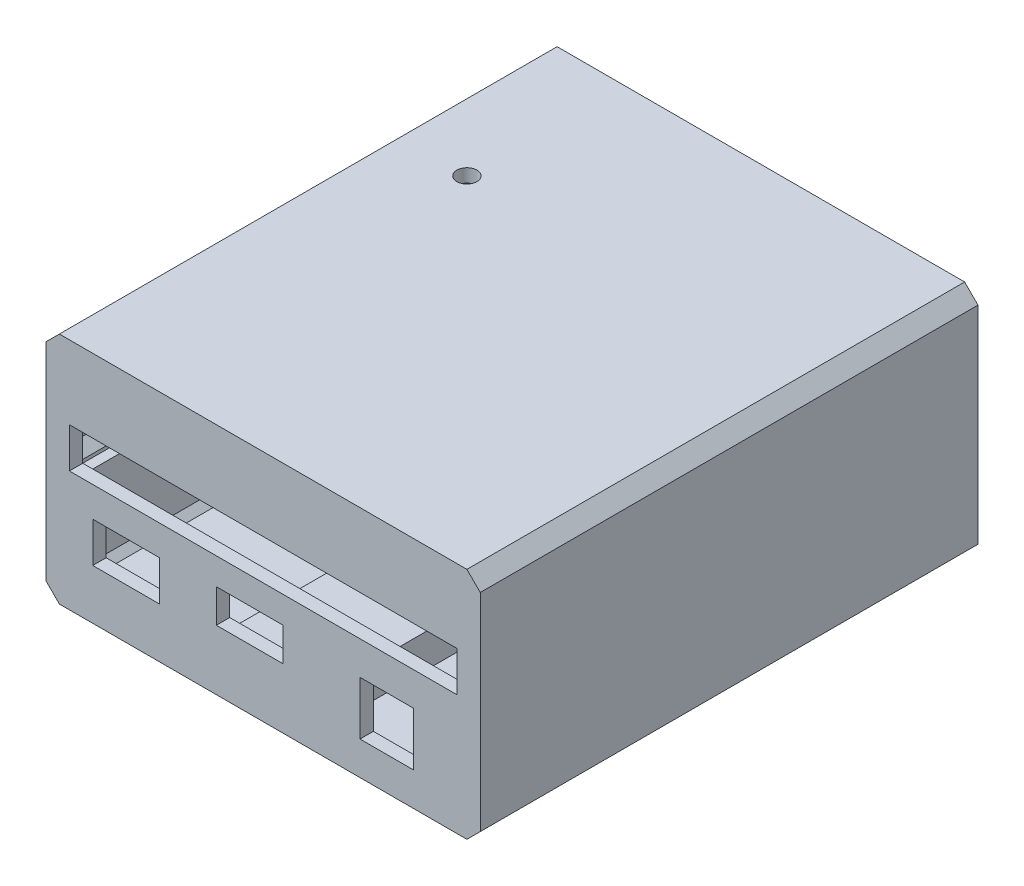
SolidWorks part; units mm, degrees
ref_plane "Alzado" through (0, 0, 0) normal (0, 0, 1) x (1, 0, 0)
ref_plane "Planta" through (0, 0, 0) normal (0, 1, 0) x (1, 0, 0)
ref_plane "Vista lateral" through (0, 0, 0) normal (1, 0, 0) x (0, 0, -1)
sketch "Croquis1" plane through (0, 0, 0) normal (0, 0, 1) x (1, 0, 0)
  line L0 (-29, 6.5) -> (-29, 0.5)
  line L1 (-32.5, -17.5) -> (32.5, -17.5)
  line L2 (-32.5, -17.5) -> (-32.5, 17.5)
  line L3 (-32.5, 17.5) -> (32.5, 17.5)
  line L4 (32.5, -17.5) -> (32.5, 17.5)
  line L5 (-32.5, -17.5) -> (32.5, 17.5) construction
  line L6 (-32.5, 17.5) -> (32.5, -17.5) construction
  line L7 (-32.5, 0.5) -> (32.5, 0.5)
  line L8 (-32.5, 0.5) -> (-32.5, 6.5)
  line L9 (-32.5, 6.5) -> (32.5, 6.5)
  line L10 (32.5, 0.5) -> (32.5, 6.5)
  line L11 (29, 6.5) -> (29, 0.5)
  line L13 (-7, -8.5) -> (3, -8.5)
  line L14 (-7, -8.5) -> (-7, -3.5)
  line L15 (-7, -3.5) -> (3, -3.5)
  line L16 (3, -8.5) -> (3, -3.5)
  line L17 (-7, -8.5) -> (3, -3.5) construction
  line L18 (-7, -3.5) -> (3, -8.5) construction
  line L19 (14.5, -12.5) -> (22.5, -12.5)
  line L20 (14.5, -12.5) -> (14.5, -4.5)
  line L21 (14.5, -4.5) -> (22.5, -4.5)
  line L22 (22.5, -12.5) -> (22.5, -4.5)
  line L23 (14.5, -12.5) -> (22.5, -4.5) construction
  line L24 (14.5, -4.5) -> (22.5, -12.5) construction
  line L25 (-25.5, -4) -> (-15.5, -4)
  line L26 (-25.5, -4) -> (-25.5, -10)
  line L27 (-25.5, -10) -> (-15.5, -10)
  line L28 (-15.5, -4) -> (-15.5, -10)
  line L29 (-25.5, -4) -> (-15.5, -10) construction
  line L30 (-25.5, -10) -> (-15.5, -4) construction
  point P0 (0, 0)
  point P14 (18.5, -8.5)
  point P15 (-2, -6)
  point P24 (-20.5, -7)
  dimension "D1" = 35
  dimension "D2" = 65
  dimension "D3" = 0.5
  dimension "D4" = 6
  dimension "D5" = 3.5
  dimension "D6" = 3.5
  dimension "D7" = 10
  dimension "D8" = 5
  dimension "D9" = 6
  dimension "D10" = 8
  dimension "D11" = 8
  dimension "D12" = 12
  dimension "D13" = 30.5
  dimension "D14" = 6
  dimension "D15" = 10
  dimension "D16" = 7
  dimension "D17" = 9
  dimension "D18" = 51
extrude "Saliente-Extruir1" add sketch "Croquis1" along normal blind 2 contours L2 L9 L4 L3 | L9 L2 L7 L0 | L9 L11 L7 L4 | L7 L2 L1 L4 L22 L19 L20 L21 L16 L13 L14 L15 L25 L28 L27 L26
sketch "Croquis2" plane through (0, 0, 0) normal (0, 0, -1) x (-1, 0, 0)
  line L0 (30.5, 15.5) -> (-30.5, 15.5)
  line L1 (-30.5, 15.5) -> (-30.5, -15.5)
  line L2 (-30.5, -15.5) -> (30.5, -15.5)
  line L3 (30.5, -15.5) -> (30.5, 15.5)
  line L4 (-32.5, -17.5) -> (32.5, -17.5)
  line L5 (32.5, -17.5) -> (32.5, 17.5)
  line L6 (32.5, 17.5) -> (-32.5, 17.5)
  line L7 (-32.5, 17.5) -> (-32.5, -17.5)
  line L8 (-32.5, -17.5) -> (32.5, -17.5)
  line L9 (32.5, -17.5) -> (32.5, 17.5)
  line L10 (32.5, 17.5) -> (-32.5, 17.5)
  line L11 (-32.5, 17.5) -> (-32.5, -17.5)
  dimension "D1" = 0
  dimension "D2" = 2
extrude "Saliente-Extruir2" add sketch "Croquis2" along normal blind 71
sketch "Croquis3" plane through (0, 0, 0) normal (0, 0, -1) x (-1, 0, 0)
  line L0 (-30.5, 0) -> (30.5, 0) construction
  line L1 (-30.5, 15.5) -> (-30.5, -15.5) construction
  line L2 (30.5, -15.5) -> (30.5, 15.5) construction
  line L3 (-30.5, 1) -> (-29, 1)
  line L4 (-29, 1) -> (-30.5, 2.5)
  line L5 (-30.5, 1) -> (-30.5, 2.5)
  line L6 (-30.5, -1) -> (-30.5, -2.5)
  line L7 (-29, -1) -> (-30.5, -2.5)
  line L8 (-30.5, -1) -> (-29, -1)
  line L9 (0, 15.5) -> (0, -15.5) construction
  line L10 (30.5, 15.5) -> (-30.5, 15.5) construction
  line L11 (-30.5, -15.5) -> (30.5, -15.5) construction
  line L12 (30.5, -1) -> (29, -1)
  line L13 (29, -1) -> (30.5, -2.5)
  line L14 (30.5, -1) -> (30.5, -2.5)
  line L15 (30.5, 1) -> (30.5, 2.5)
  line L16 (29, 1) -> (30.5, 2.5)
  line L17 (30.5, 1) -> (29, 1)
  dimension "D1" = 1.5
  dimension "D2" = 1.5
  dimension "D3" = 1
extrude "Saliente-Extruir3" add sketch "Croquis3" along normal blind 70
sketch "Croquis9" plane through (0, 17.5, 0) normal (0, 1, 0) x (1, 0, 0)
  circle A0 centre (-20.5, 49) radius 1.5
  dimension "D1" = 20.5
  dimension "D3" = 3
  dimension "D4" = 49
extrude "Cortar-Extruir2" cut sketch "Croquis9" against normal up to next
chamfer "Chaflán3" distance 2 angle 45 4 edges at (32.5, -17.5, -34.5) (-32.5, -17.5, -34.5) (32.5, 17.5, -34.5) (-32.5, 17.5, -34.5)
chamfer "Chaflán2" distance 1 angle 45 4 edges at (-30.5, 15.5, -35.5) (-30.5, -15.5, -35.5) (30.5, -15.5, -35.5) (30.5, 15.5, -35.5)
sketch "Sketch1" plane through (0, 0, -71) normal (0, 0, -1) x (-1, 0, 0)
  line L0 (-31.55, 15.1065) -> (-31.55, -15.1065)
  line L1 (-31.55, -15.1065) -> (-30.1065, -16.55)
  line L2 (-30.1065, -16.55) -> (30.1065, -16.55)
  line L3 (30.1065, -16.55) -> (31.55, -15.1065)
  line L4 (31.55, -15.1065) -> (31.55, 15.1065)
  line L5 (31.55, 15.1065) -> (30.1065, 16.55)
  line L6 (30.1065, 16.55) -> (-30.1065, 16.55)
  line L7 (-30.1065, 16.55) -> (-31.55, 15.1065)
  line L8 (-32.5, 15.5) -> (-32.5, -15.5)
  line L9 (-32.5, -15.5) -> (-30.5, -17.5)
  line L10 (-30.5, -17.5) -> (30.5, -17.5)
  line L11 (30.5, -17.5) -> (32.5, -15.5)
  line L12 (32.5, -15.5) -> (32.5, 15.5)
  line L13 (32.5, 15.5) -> (30.5, 17.5)
  line L14 (30.5, 17.5) -> (-30.5, 17.5)
  line L15 (-30.5, 17.5) -> (-32.5, 15.5)
  line L16 (-32.5, 15.5) -> (-32.5, -15.5)
  line L17 (-32.5, -15.5) -> (-30.5, -17.5)
  line L18 (-30.5, -17.5) -> (30.5, -17.5)
  line L19 (30.5, -17.5) -> (32.5, -15.5)
  line L20 (32.5, -15.5) -> (32.5, 15.5)
  line L21 (32.5, 15.5) -> (30.5, 17.5)
  line L22 (30.5, 17.5) -> (-30.5, 17.5)
  line L23 (-30.5, 17.5) -> (-32.5, 15.5)
  dimension "D1" = 0
  dimension "D2" = 0.95
extrude "Boss-Extrude1" add sketch "Sketch1" along normal blind 1.5
chamfer "Chamfer1" distance 0.1 distance2 1.5 8 edges at (0, -16.55, -72.5) (-30.8282, -15.8282, -72.5) (-31.55, 0, -72.5) (-30.8282, 15.8282, -72.5) (0, 16.55, -72.5) (30.8282, 15.8282, -72.5) (31.55, 0, -72.5) (30.8282, -15.8282, -72.5)
sketch "Sketch2" plane through (0, 0, -72.5) normal (0, 0, -1) x (-1, 0, 0)
  line L0 (-31.65, -15.1479) -> (-31.65, 15.1479) construction
  line L1 (-32.15, -1) -> (-31.15, -1)
  line L2 (-32.15, -1) -> (-32.15, 1)
  line L3 (-32.15, 1) -> (-31.15, 1)
  line L4 (-31.15, -1) -> (-31.15, 1)
  line L5 (-32.15, -1) -> (-31.15, 1) construction
  line L6 (-32.15, 1) -> (-31.15, -1) construction
  line L7 (31.65, 15.1479) -> (31.65, -15.1479) construction
  line L8 (31.15, -1) -> (32.15, -1)
  line L9 (31.15, -1) -> (31.15, 1)
  line L10 (31.15, 1) -> (32.15, 1)
  line L11 (32.15, -1) -> (32.15, 1)
  line L12 (31.15, -1) -> (32.15, 1) construction
  line L13 (31.15, 1) -> (32.15, -1) construction
  point P0 (-31.65, 0)
  point P7 (31.65, 0)
  dimension "D1" = 2
  dimension "D2" = 1
  dimension "D3" = 1
  dimension "D4" = 2
extrude "Boss-Extrude2" add sketch "Sketch2" against normal blind 0.5
sketch "Sketch3" plane through (0, -17.5, 0) normal (0, -1, 0) x (1, 0, 0)
  line L0 (0, 2) -> (0, -18) construction
  line L1 (-30.5, 2) -> (30.5, 2) construction
  line L3 (7.5, -8) -> (-7.5, -8)
  line L4 (7.5, -8) -> (7.5, -28)
  line L5 (7.5, -28) -> (-7.5, -28)
  line L6 (-7.5, -8) -> (-7.5, -28)
  line L7 (7.5, -8) -> (-7.5, -28) construction
  line L8 (7.5, -28) -> (-7.5, -8) construction
  dimension "D1" = 20
  dimension "D2" = 15
  dimension "D3" = 20
extrude "Boss-Extrude3" add sketch "Sketch3" against normal blind 7
sketch "Sketch4" plane through (0, -17.5, 0) normal (0, -1, 0) x (1, 0, 0)
  line L0 (0, 2) -> (0, -18) construction
  line L1 (-30.5, 2) -> (30.5, 2) construction
  line L3 (-6.5, -27) -> (6.5, -27)
  line L4 (-6.5, -27) -> (-6.5, -9)
  line L5 (-6.5, -9) -> (6.5, -9)
  line L6 (6.5, -27) -> (6.5, -9)
  line L7 (-6.5, -27) -> (6.5, -9) construction
  line L8 (-6.5, -9) -> (6.5, -27) construction
  dimension "D1" = 20
  dimension "D2" = 13
  dimension "D3" = 18
extrude "Cut-Extrude1" cut sketch "Sketch4" against normal blind 5
sketch "Sketch5" plane through (0, 0, -9) normal (0, 0, -1) x (-1, 0, 0)
  line L1 (6.5, -17.5) -> (-6.5, -17.5)
  line L2 (6.5, -17.5) -> (6.5, -15)
  line L3 (6.5, -15) -> (-6.5, -15)
  line L4 (-6.5, -17.5) -> (-6.5, -15)
  line L5 (-6.5, -12.5) -> (-6.5, -17.5) construction
  point P4 (-6.0318, -15.0053)
  point P7 (0, 0)
  dimension "D1" = 2.5
extrude "Boss-Extrude4" add sketch "Sketch5" along normal blind 12
chamfer "Chamfer2" distance 5 angle 60 1 edges at (0, -15.5, -28)
chamfer "Chamfer3" distance 5 angle 60 1 edges at (0, -17.5, -27)
chamfer "Chamfer4" distance 3 angle 30 1 edges at (0, -15, -21)
sketch "Sketch6" plane through (0, 0, -8) normal (0, 0, 1) x (1, 0, 0)
  line L4 (-7.5, -10.5) -> (-7.5, -15.5)
  line L5 (-7.5, -15.5) -> (7.5, -15.5)
  line L6 (7.5, -15.5) -> (7.5, -10.5)
  line L7 (7.5, -10.5) -> (-7.5, -10.5)
  line L8 (-7.5, -10.5) -> (-7.5, -15.5)
  line L9 (-7.5, -15.5) -> (7.5, -15.5)
  line L10 (7.5, -15.5) -> (7.5, -10.5)
  line L11 (7.5, -10.5) -> (-7.5, -10.5)
  dimension "D1" = 0
extrude "Boss-Extrude5" add sketch "Sketch6" along normal up to next
sketch "Sketch7" plane through (0, -3.4558, 1.9952) normal (0, 0.866, -0.5) x (1, 0, 0)
  line L0 (6.5, 23.0885) -> (-6.5, 23.0885) construction
  line L1 (6.5, 23.0885) -> (-3.3659, 23.0885)
  line L2 (6.5, 23.0885) -> (6.5, 22.5885)
  line L3 (6.5, 22.5885) -> (-3.3659, 22.5885)
  line L4 (-3.3659, 23.0885) -> (-3.3659, 22.5885)
  line L5 (6.5, 26.5526) -> (6.5, 23.0885) construction
  dimension "D1" = 0.5
extrude "Boss-Extrude6" add sketch "Sketch7" along direction (0, 0, 1) on the side against the normal offset from surface (1 mm away) 8
